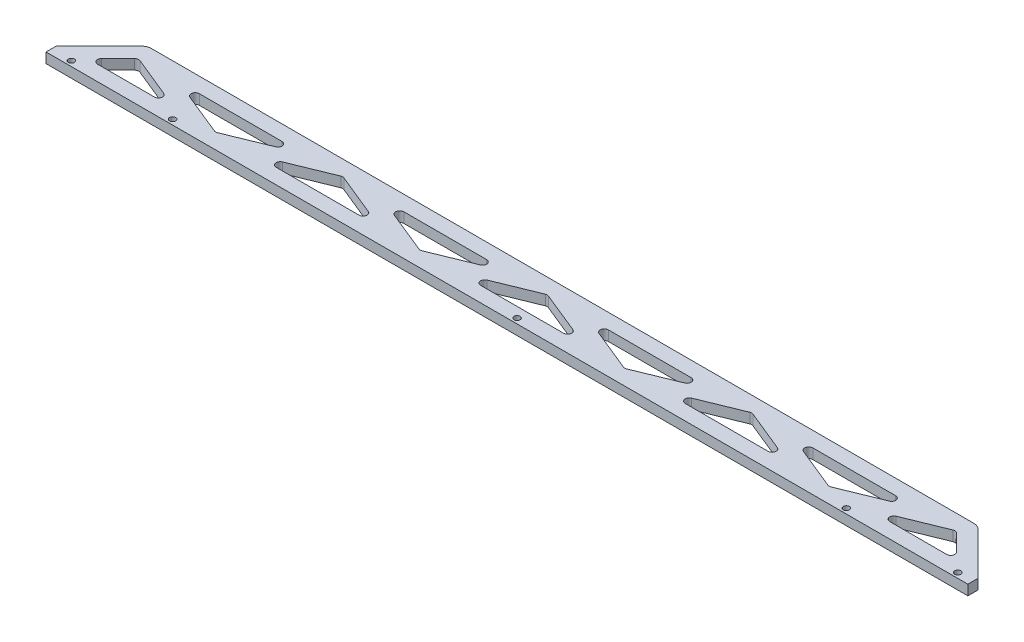
SolidWorks part; units mm, degrees
ref_plane "Front Plane" through (0, 0, 0) normal (0, 0, 1) x (1, 0, 0)
ref_plane "Top Plane" through (0, 0, 0) normal (0, 1, 0) x (1, 0, 0)
ref_plane "Right Plane" through (0, 0, 0) normal (1, 0, 0) x (0, 0, -1)
sketch "Sketch1" plane through (0, 0, 0) normal (0, 1, 0) x (1, 0, 0)
  line L0 (0, 0) -> (577.85, 0)
  line L2 (549.275, 34.925) -> (28.575, 34.925)
  line L4 (0, 0) -> (0, 6.35)
  line L7 (0, 6.35) -> (28.575, 34.925)
  line L8 (577.85, 0) -> (577.85, 6.35)
  line L9 (577.85, 6.35) -> (549.275, 34.925)
  dimension "D1" = 34.925
  dimension "D2" = 577.85
  dimension "D3" = 6.35
  dimension "D4" = 135
extrude "Boss-Extrude1" add sketch "Sketch1" along normal blind 6.35 contours L7 L2 L9 L8 L0 L4
fillet "Fillet1" radius 6.35 2 edges at (549.275, 3.175, -34.925) (28.575, 3.175, -34.925)
sketch "Sketch2" plane through (0, 6.35, 0) normal (0, 1, 0) x (1, 0, 0)
  line L0 (16.6454, 9.525) -> (71.4155, 9.525)
  line L1 (71.4155, 9.525) -> (32.5204, 25.4)
  line L2 (32.5204, 25.4) -> (16.6454, 9.525)
  line L3 (57.7264, 25.4) -> (96.6215, 9.525)
  line L4 (96.6215, 9.525) -> (135.5167, 25.4)
  line L5 (135.5167, 25.4) -> (57.7264, 25.4)
  line L6 (0, 6.35) -> (26.7151, 33.0651) construction
  line L7 (96.6215, 9.525) -> (96.6215, 25.4) construction
  line L8 (546.6447, 34.925) -> (31.2053, 34.925) construction
  line L9 (0, 0) -> (577.85, 0) construction
  line L10 (57.7264, 25.4) -> (19.05, 25.4) construction
  line L11 (558.8, 25.4) -> (520.1236, 25.4) construction
  line L12 (577.85, 6.35) -> (551.1349, 33.0651) construction
  line L13 (57.7264, 25.4) -> (520.1236, 25.4) construction
  line L14 (121.8276, 9.525) -> (160.7227, 25.4)
  line L15 (160.7227, 25.4) -> (199.6178, 9.525)
  line L16 (199.6178, 9.525) -> (121.8276, 9.525)
  line L17 (185.9287, 25.4) -> (224.8238, 9.525)
  line L18 (224.8238, 9.525) -> (263.719, 25.4)
  line L19 (263.719, 25.4) -> (185.9287, 25.4)
  line L20 (250.0299, 9.525) -> (288.925, 25.4)
  line L21 (288.925, 25.4) -> (327.8201, 9.525)
  line L22 (327.8201, 9.525) -> (250.0299, 9.525)
  line L23 (314.131, 25.4) -> (353.0262, 9.525)
  line L24 (353.0262, 9.525) -> (391.9213, 25.4)
  line L25 (391.9213, 25.4) -> (314.131, 25.4)
  line L26 (378.2322, 9.525) -> (417.1273, 25.4)
  line L27 (417.1273, 25.4) -> (456.0224, 9.525)
  line L28 (456.0224, 9.525) -> (378.2322, 9.525)
  line L29 (442.3333, 25.4) -> (481.2285, 9.525)
  line L30 (481.2285, 9.525) -> (520.1236, 25.4)
  line L31 (520.1236, 25.4) -> (442.3333, 25.4)
  line L32 (131.8028, 23.8842) -> (135.4022, 15.0655) construction
  line L33 (194.7237, 11.5225) -> (198.323, 20.3413) construction
  line L34 (258.9928, 23.471) -> (262.5921, 14.6523) construction
  line L35 (343.1239, 13.5666) -> (339.5245, 4.7479) construction
  line L36 (401.2708, 29.216) -> (404.8702, 20.3973) construction
  line L37 (494.7767, -6.2925) -> (498.3761, 2.5262) construction
  line L38 (561.2046, 9.525) -> (506.4345, 9.525)
  line L39 (561.2046, 9.525) -> (545.3296, 25.4)
  line L40 (545.3296, 25.4) -> (506.4345, 9.525)
  dimension "D1" = 9.525
  dimension "D2" = 9.525
  dimension "D3" = 9.525
  dimension "D4" = 9.525
  dimension "D5" = 9.525
  dimension "D6" = 9.525
  dimension "D7" = 9.525
extrude "Cut-Extrude1" cut sketch "Sketch2" against normal blind 6.35
fillet "Fillet2" radius 2.54 27 edges at (545.3296, 3.175, -25.4) (442.3333, 3.175, -25.4) (391.9213, 3.175, -25.4) (417.1273, 3.175, -25.4) (288.925, 3.175, -25.4) (314.131, 3.175, -25.4) (185.9287, 3.175, -25.4) (263.719, 3.175, -25.4) (520.1236, 3.175, -25.4) (481.2285, 3.175, -9.525) (353.0262, 3.175, -9.525) (224.8238, 3.175, -9.525) (250.0299, 3.175, -9.525) (378.2322, 3.175, -9.525) (506.4345, 3.175, -9.525) (561.2046, 3.175, -9.525) (456.0224, 3.175, -9.525) (327.8201, 3.175, -9.525) (199.6178, 3.175, -9.525) (121.8276, 3.175, -9.525) (160.7227, 3.175, -25.4) (135.5167, 3.175, -25.4) (57.7264, 3.175, -25.4) (96.6215, 3.175, -9.525) (71.4155, 3.175, -9.525) (32.5204, 3.175, -25.4) (16.6454, 3.175, -9.525)
hole_wizard "#6 Clearance Hole1" positions "Sketch3" profile "Sketch4" hole size "#6" standard "ANSI Inch"
sketch "Sketch3" plane through (0, 6.35, 0) normal (0, 1, 0) x (1, 0, 0)
  line L0 (0, 0) -> (0, 6.35) construction
  line L1 (0, 0) -> (577.85, 0) construction
  line L2 (577.85, 0) -> (577.85, 6.35) construction
  point P0 (12.7, 3.175)
  point P7 (76.2, 3.175)
  point P11 (292.1, 3.175)
  point P16 (568.325, 3.175)
  point P18 (498.475, 3.175)
  point P23 (0, 0)
  dimension "D1" = 12.7
  dimension "D2" = 3.175
  dimension "D3" = 76.2
  dimension "D4" = 292.1
  dimension "D5" = 9.525
  dimension "D6" = 69.85
sketch "Sketch4" plane through (12.7, 6.35, -3.175) normal (1, 0, 0) x (0, 0, 1)
  line L0 (0, 0) -> (0, 13.8408)
  line L1 (0, 13.8408) -> (1.8986, 12.7)
  line L2 (1.8986, 12.7) -> (1.8986, 0)
  line L5 (1.8986, 0) -> (0, 0)
  line L10 (0, 13.8408) -> (-1.8986, 12.7) construction
  line L11 (0, -6.35) -> (0, 107.95) construction
  dimension "Hole Dia." = 3.7973
  dimension "Hole Depth" = 12.7
  dimension "Drill Angle" = 118
